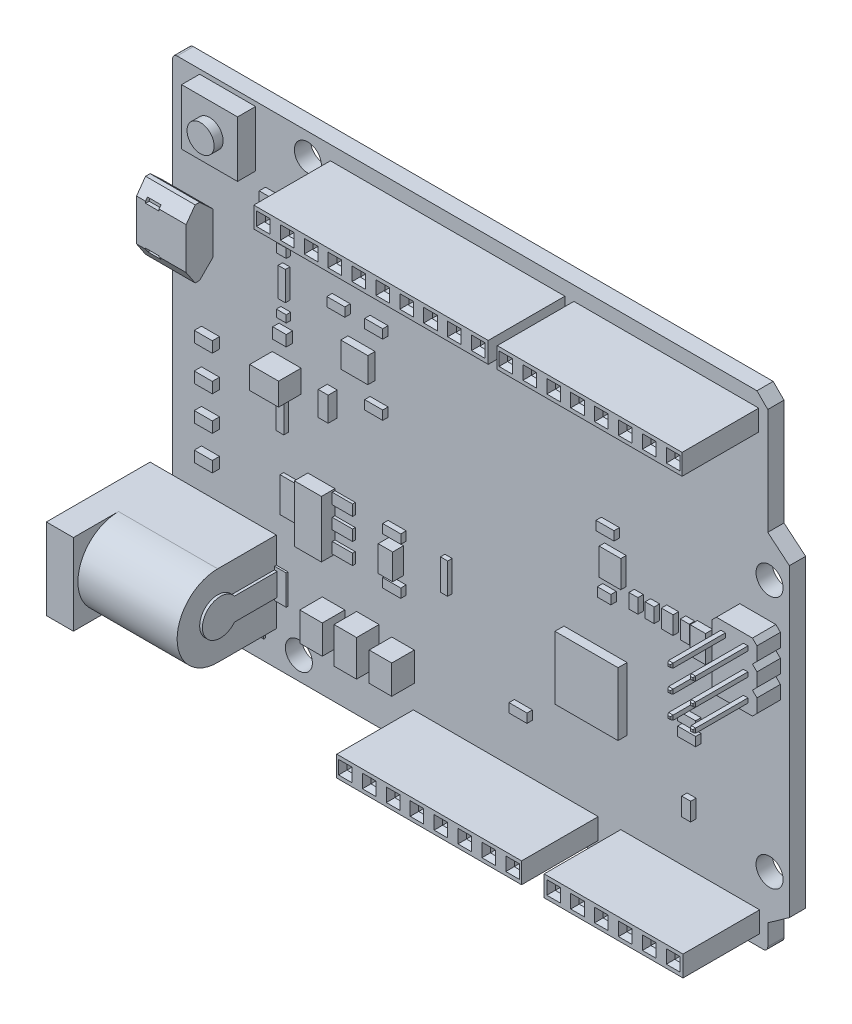
SolidWorks part; units mm, degrees
ref_plane "Front Plane" through (0, 0, 0) normal (0, 0, 1) x (1, 0, 0)
ref_plane "Top Plane" through (0, 0, 0) normal (0, 1, 0) x (1, 0, 0)
ref_plane "Right Plane" through (0, 0, 0) normal (1, 0, 0) x (0, 0, -1)
sketch "Sketch1" plane through (0, 0, 0) normal (0, 0, 1) x (1, 0, 0)
  line L0 (66, -1.2) -> (66, -13)
  line L1 (0.5, 0) -> (64.8, 0)
  line L2 (0, -0.5) -> (0, -52.8)
  line L3 (0.5, -53.3) -> (65.5, -53.3)
  line L4 (68.4, -15) -> (68.4, -48.8)
  line L5 (66, -13) -> (68.4, -15)
  line L6 (68.4, -48.8) -> (66, -50.5)
  line L7 (66, -50.5) -> (66, -52.8)
  line L8 (64.8, 0) -> (66, -1.2)
  arc A0 (65.5, -53.3) -> (66, -52.8) centre (65.5, -52.8) ccw
  arc A1 (0, -52.8) -> (0.5, -53.3) centre (0.5, -52.8) ccw
  arc A2 (0.5, 0) -> (0, -0.5) centre (0.5, -0.5) ccw
  point P12 (66, -53.3)
  point P15 (0, -53.3)
  point P18 (0, 0)
  dimension "D5" = 0.5
  dimension "D1" = 68.4
  dimension "D2" = 53.3
  dimension "D3" = 66
  dimension "D4" = 66
  dimension "D6" = 15
  dimension "D7" = 48.8
  dimension "D8" = 50.5
  dimension "D9" = 45
  dimension "D10" = 1.2
extrude "Boss-Extrude1" add sketch "Sketch1" along normal blind 1.8
sketch "Sketch2" plane through (0, 0, 1.8) normal (0, 0, 1) x (1, 0, 0)
  line L0 (0, -0.5) -> (0, -52.8) construction
  line L1 (64.8, 0) -> (0.5, 0) construction
  line L2 (68.4, -48.8) -> (68.4, -15) construction
  line L3 (0.5, -53.3) -> (65.5, -53.3) construction
  point P0 (15, -2.5)
  point P1 (66.2, -17.5)
  point P2 (66.2, -45.5)
  point P3 (14, -50.8)
  dimension "D1" = 15
  dimension "D2" = 2.5
  dimension "D3" = 2.2
  dimension "D4" = 2.2
  dimension "D5" = 2.5
  dimension "D6" = 14
  dimension "D7" = 17.5
  dimension "D8" = 45.5
hole_wizard "Ø3.0 (3) Diameter Hole2" positions "Sketch6" profile "Sketch7" hole size "Ø3.0" standard "ISO" end condition through all
sketch "Sketch6" plane through (0, 0, 1.8) normal (0, 0, 1) x (1, 0, 0)
  point P0 (15, -2.5)
  point P3 (66.2, -17.5)
  point P6 (66.2, -45.5)
  point P9 (14, -50.8)
sketch "Sketch7" plane through (15, -2.5, 1.8) normal (1, 0, 0) x (0, -1, 0)
  line L0 (0, 0) -> (0, 1.8)
  line L1 (0, 1.8) -> (1.5, 1.8)
  line L2 (1.5, 1.8) -> (1.5, 0)
  line L5 (1.5, 0) -> (0, 0)
  line L11 (0, -6.35) -> (0, 107.95) construction
  dimension "Thru Hole Dia." = 3
  dimension "Thru Hole Depth" = 1.8
sketch "Sketch8" plane through (0, 0, 1.8) normal (0, 0, 1) x (1, 0, 0)
  line L0 (0.5, -53.3) -> (65.5, -53.3) construction
  line L1 (44.5, -1.5683) -> (65, -1.5683)
  line L2 (44.5, -1.5683) -> (44.5, -3.8683)
  line L3 (44.5, -3.8683) -> (65, -3.8683)
  line L4 (65, -1.5683) -> (65, -3.8683)
  line L5 (17.5, -1.5683) -> (43.5, -1.5683)
  line L6 (17.5, -1.5683) -> (17.5, -3.8683)
  line L7 (17.5, -3.8683) -> (43.5, -3.8683)
  line L8 (43.5, -1.5683) -> (43.5, -3.8683)
  line L9 (65.1, -52) -> (49.7, -52)
  line L10 (65.1, -52) -> (65.1, -49.7)
  line L11 (65.1, -49.7) -> (49.7, -49.7)
  line L12 (49.7, -52) -> (49.7, -49.7)
  line L13 (47.2, -52) -> (26.7, -52)
  line L14 (47.2, -52) -> (47.2, -49.7)
  line L15 (47.2, -49.7) -> (26.7, -49.7)
  line L16 (26.7, -52) -> (26.7, -49.7)
  line L17 (68.4, -48.8) -> (68.4, -15) construction
  line L18 (66, -13) -> (66, -1.2) construction
  dimension "D1" = 2.3
  dimension "D2" = 2.3
  dimension "D3" = 2.3
  dimension "D4" = 2.3
  dimension "D5" = 15.4
  dimension "D6" = 1.3
  dimension "D7" = 1.3
  dimension "D8" = 20.5
  dimension "D9" = 2.5
  dimension "D10" = 3.3
  dimension "D11" = 1
  dimension "D12" = 1
  dimension "D13" = 20.5
  dimension "D14" = 26
extrude "Boss-Extrude2" add sketch "Sketch8" along normal blind 8.5
sketch "Sketch10" plane through (0, 0, 10.3) normal (0, 0, 1) x (1, 0, 0)
  line L0 (26.7, -49.7) -> (26.7, -52) construction
  line L1 (26.9, -50.1) -> (28.4, -50.1)
  line L2 (26.9, -50.1) -> (26.9, -51.6)
  line L3 (26.9, -51.6) -> (28.4, -51.6)
  line L4 (28.4, -50.1) -> (28.4, -51.6)
  line L5 (26.7, -52) -> (47.2, -52) construction
  dimension "D1" = 1.5
  dimension "D2" = 1.5
  dimension "D3" = 0.2
  dimension "D4" = 0.4
extrude "Cut-Extrude1" cut sketch "Sketch10" against normal blind 8.5 draft 20
sketch "Sketch11" plane through (0, 0, 10.3) normal (0, 0, 1) x (1, 0, 0)
  line L0 (27.65, -50.85) -> (28.4, -51.6) construction
  line L1 (27.15, -50.35) -> (28.15, -50.35)
  line L2 (27.15, -50.35) -> (27.15, -51.35)
  line L3 (27.15, -51.35) -> (28.15, -51.35)
  line L4 (28.15, -50.35) -> (28.15, -51.35)
  line L5 (27.15, -50.35) -> (28.15, -51.35) construction
  line L6 (27.15, -51.35) -> (28.15, -50.35) construction
  point P0 (27.65, -50.85)
  dimension "D1" = 1
  dimension "D2" = 1
extrude "Cut-Extrude2" cut sketch "Sketch11" against normal blind 8.5
pattern_linear "LPattern1" count 8 spacing 2.65 along (1, 0, 0) of "Cut-Extrude2", "Cut-Extrude1"
sketch "Sketch12" plane through (0, 0, 10.3) normal (0, 0, 1) x (1, 0, 0)
  line L0 (65.1, -49.7) -> (49.7, -49.7) construction
  line L1 (50, -50.1) -> (51.5, -50.1)
  line L2 (50, -50.1) -> (50, -51.6)
  line L3 (50, -51.6) -> (51.5, -51.6)
  line L4 (51.5, -50.1) -> (51.5, -51.6)
  line L5 (49.7, -49.7) -> (49.7, -52) construction
  dimension "D1" = 1.5
  dimension "D2" = 1.5
  dimension "D3" = 0.4
  dimension "D4" = 0.3
extrude "Cut-Extrude3" cut sketch "Sketch12" against normal blind 8.5 draft 20
sketch "Sketch14" plane through (0, 0, 10.3) normal (0, 0, 1) x (1, 0, 0)
  line L0 (50.75, -50.85) -> (51.5, -50.1) construction
  line L1 (50.25, -50.35) -> (51.25, -50.35)
  line L2 (50.25, -50.35) -> (50.25, -51.35)
  line L3 (50.25, -51.35) -> (51.25, -51.35)
  line L4 (51.25, -50.35) -> (51.25, -51.35)
  line L5 (50.25, -50.35) -> (51.25, -51.35) construction
  line L6 (50.25, -51.35) -> (51.25, -50.35) construction
  line L7 (50.75, -50.85) -> (50, -51.6) construction
  line L8 (51.5, -50.1) -> (50, -50.1) construction
  line L9 (50, -50.1) -> (50, -51.6) construction
  point P0 (50.75, -50.85)
  dimension "D1" = 1
  dimension "D2" = 1
  dimension "D3" = 0.25
  dimension "D4" = 0.25
extrude "Cut-Extrude4" cut sketch "Sketch14" against normal blind 8.5
pattern_linear "LPattern2" count 6 spacing 2.65 along (1, 0, 0) of "Cut-Extrude4", "Cut-Extrude3"
sketch "Sketch15" plane through (0, 0, 10.3) normal (0, 0, 1) x (1, 0, 0)
  line L0 (17.5, -1.5683) -> (17.5, -3.8683) construction
  line L1 (17.8, -1.9683) -> (19.3, -1.9683)
  line L2 (17.8, -1.9683) -> (17.8, -3.4683)
  line L3 (17.8, -3.4683) -> (19.3, -3.4683)
  line L4 (19.3, -1.9683) -> (19.3, -3.4683)
  line L5 (43.5, -1.5683) -> (17.5, -1.5683) construction
  point P4 (17.5, -2.7183)
  dimension "D1" = 0.3
  dimension "D2" = 1.5
  dimension "D3" = 0.4
  dimension "D4" = 1.5
extrude "Cut-Extrude5" cut sketch "Sketch15" against normal blind 8.5 draft 20
sketch "Sketch16" plane through (0, 0, 10.3) normal (0, 0, 1) x (1, 0, 0)
  line L0 (18.55, -2.7183) -> (19.3, -3.4683) construction
  line L1 (18.0652, -2.2335) -> (19.0652, -2.2335)
  line L2 (18.0652, -2.2335) -> (18.0652, -3.2335)
  line L3 (18.0652, -3.2335) -> (19.0652, -3.2335)
  line L4 (19.0652, -2.2335) -> (19.0652, -3.2335)
  line L5 (18.0652, -2.2335) -> (19.0652, -3.2335) construction
  line L6 (18.0652, -3.2335) -> (19.0652, -2.2335) construction
  point P0 (18.5652, -2.7335)
  dimension "D1" = 1
extrude "Cut-Extrude6" cut sketch "Sketch16" against normal blind 8.5
pattern_linear "LPattern3" count 10 spacing 2.65 along (1, 0, 0) of "Cut-Extrude5", "Cut-Extrude6"
sketch "Sketch17" plane through (0, 0, 10.3) normal (0, 0, 1) x (1, 0, 0)
  line L0 (65, -1.5683) -> (44.5, -1.5683) construction
  line L1 (44.7, -1.9683) -> (46.2, -1.9683)
  line L2 (44.7, -1.9683) -> (44.7, -3.4683)
  line L3 (44.7, -3.4683) -> (46.2, -3.4683)
  line L4 (46.2, -1.9683) -> (46.2, -3.4683)
  line L5 (44.5, -1.5683) -> (44.5, -3.8683) construction
  dimension "D1" = 0.4
  dimension "D2" = 1.5
  dimension "D3" = 1.5
  dimension "D4" = 0.2
extrude "Cut-Extrude7" cut sketch "Sketch17" against normal blind 8.5 draft 20
sketch "Sketch18" plane through (0, 0, 10.3) normal (0, 0, 1) x (1, 0, 0)
  line L0 (45.45, -2.7183) -> (46.2, -3.4683) construction
  line L1 (44.95, -2.2183) -> (45.95, -2.2183)
  line L2 (44.95, -2.2183) -> (44.95, -3.2183)
  line L3 (44.95, -3.2183) -> (45.95, -3.2183)
  line L4 (45.95, -2.2183) -> (45.95, -3.2183)
  line L5 (44.95, -2.2183) -> (45.95, -3.2183) construction
  line L6 (44.95, -3.2183) -> (45.95, -2.2183) construction
  point P0 (45.45, -2.7183)
  dimension "D1" = 1
extrude "Cut-Extrude8" cut sketch "Sketch18" against normal blind 8.5
pattern_linear "LPattern4" count 8 spacing 2.65 along (1, 0, 0) of "Cut-Extrude8", "Cut-Extrude7"
sketch "Sketch19" plane through (0, 0, 1.8) normal (0, 0, 1) x (1, 0, 0)
  line L0 (68.4, -48.8) -> (68.4, -15) construction
  line L1 (62.4, -21.4) -> (67.4, -21.4)
  line L2 (62.4, -21.4) -> (62.4, -23.4)
  line L3 (62.4, -28.9) -> (67.4, -28.9)
  line L4 (67.4, -21.4) -> (67.4, -23.4)
  line L5 (64.8, 0) -> (0.5, 0) construction
  line L6 (66.9, -26.4) -> (67.4, -25.9)
  line L7 (66.9, -26.4) -> (67.4, -26.9)
  line L10 (62.9, -26.4) -> (62.4, -26.9)
  line L11 (62.9, -26.4) -> (62.4, -25.9)
  line L12 (66.9, -23.9) -> (67.4, -23.4)
  line L13 (66.9, -23.9) -> (67.4, -24.4)
  line L14 (62.9, -23.9) -> (62.4, -24.4)
  line L15 (62.9, -23.9) -> (62.4, -23.4)
  line L16 (62.4, -24.4) -> (62.4, -25.9)
  line L17 (62.4, -26.9) -> (62.4, -28.9)
  line L18 (67.4, -24.4) -> (67.4, -25.9)
  line L19 (67.4, -26.9) -> (67.4, -28.9)
  dimension "D1" = 5
  dimension "D2" = 7.5
  dimension "D3" = 5
  dimension "D4" = 1
  dimension "D5" = 21.4
  dimension "D6" = 2.5
  dimension "D7" = 5
  dimension "D8" = 90
  dimension "D9" = 135
  dimension "D10" = 135
  dimension "D11" = 90
  dimension "D12" = 90
  dimension "D13" = 90
  dimension "D14" = 135
  dimension "D15" = 135
  dimension "D16" = 0.5
  dimension "D17" = 0.5
  dimension "D18" = 0.5
  dimension "D19" = 0.5
extrude "Boss-Extrude3" add sketch "Sketch19" along normal blind 2.6
chamfer "Chamfer1" distance 0.5 angle 45 4 edges at (62.4, -21.4, 3.1) (62.4, -28.9, 3.1) (67.4, -28.9, 3.1) (67.4, -21.4, 3.1)
sketch "Sketch20" plane through (0, 0, 4.4) normal (0, 0, 1) x (1, 0, 0)
  line L0 (66.9, -21.4) -> (62.9, -21.4) construction
  line L1 (63.4, -22.4) -> (63.9, -22.4)
  line L2 (63.4, -22.4) -> (63.4, -22.9)
  line L3 (63.4, -22.9) -> (63.9, -22.9)
  line L4 (63.9, -22.4) -> (63.9, -22.9)
  line L5 (65.9, -22.4) -> (66.4, -22.4)
  line L6 (65.9, -22.4) -> (65.9, -22.9)
  line L7 (65.9, -22.9) -> (66.4, -22.9)
  line L8 (66.4, -22.4) -> (66.4, -22.9)
  line L9 (62.4, -21.9) -> (62.4, -23.4) construction
  line L10 (67.4, -23.4) -> (67.4, -21.9) construction
  point P11 (62.4, -22.65)
  dimension "D1" = 0.5
  dimension "D2" = 0.5
  dimension "D3" = 0.5
  dimension "D4" = 0.5
  dimension "D5" = 2
  dimension "D6" = 1
  dimension "D7" = 1
  dimension "D8" = 1
  dimension "D9" = 1
  dimension "D10" = 1
extrude "Boss-Extrude4" add sketch "Sketch20" along normal blind 6
chamfer "Chamfer2" distance 0.2 angle 30 8 edges at (66.4, -22.65, 10.4) (66.15, -22.9, 10.4) (65.9, -22.65, 10.4) (66.15, -22.4, 10.4) (63.9, -22.65, 10.4) (63.65, -22.4, 10.4) (63.4, -22.65, 10.4) (63.65, -22.9, 10.4) first distance on face at (66.4, -22.65, 7.4) first distance on face at (66.15, -22.9, 7.4) first distance on face at (65.9, -22.65, 7.4) first distance on face at (66.15, -22.4, 7.4) first distance on face at (63.9, -22.65, 7.4) first distance on face at (63.65, -22.4, 7.4) first distance on face at (63.4, -22.65, 7.4) first distance on face at (63.65, -22.9, 7.4)
pattern_linear "LPattern6" count 3 spacing 2.5 along (0, -1, 0) of "Chamfer2", "Boss-Extrude4"
sketch "Sketch21" plane through (0, 0, 1.8) normal (0, 0, 1) x (1, 0, 0)
  line L0 (68.4, -48.8) -> (68.4, -15) construction
  line L1 (43.4, -33.3) -> (50.4, -33.3)
  line L2 (43.4, -33.3) -> (43.4, -40.3)
  line L3 (43.4, -40.3) -> (50.4, -40.3)
  line L4 (50.4, -33.3) -> (50.4, -40.3)
  line L5 (0.5, -53.3) -> (65.5, -53.3) construction
  dimension "D1" = 7
  dimension "D2" = 7
  dimension "D3" = 18
  dimension "D4" = 20
extrude "Boss-Extrude5" add sketch "Sketch21" along normal blind 1
sketch "Sketch22" plane through (0, 0, 1.8) normal (0, 0, 1) x (1, 0, 0)
  line L0 (62.4, -26.9) -> (62.4, -28.4) construction
  line L1 (58.2, -25.3683) -> (59.9, -25.3683)
  line L2 (58.2, -25.3683) -> (58.2, -28.3683)
  line L3 (58.2, -28.3683) -> (59.9, -28.3683)
  line L4 (59.9, -25.3683) -> (59.9, -28.3683)
  line L5 (44.5, -3.8683) -> (65, -3.8683) construction
  point P4 (62.4, -27.65)
  dimension "D1" = 3
  dimension "D2" = 1.7
  dimension "D3" = 2.5
  dimension "D4" = 21.5
extrude "Boss-Extrude6" add sketch "Sketch22" along normal blind 0.8
sketch "Sketch23" plane through (0, 0, 1.8) normal (0, 0, 1) x (1, 0, 0)
  line L0 (58.2, -25.3683) -> (58.2, -28.3683) construction
  line L1 (56.9, -25.5683) -> (57.9, -25.5683)
  line L2 (56.9, -25.5683) -> (56.9, -27.5683)
  line L3 (56.9, -27.5683) -> (57.9, -27.5683)
  line L4 (57.9, -25.5683) -> (57.9, -27.5683)
  line L5 (54.8, -25.5683) -> (56.1, -25.5683)
  line L6 (54.8, -25.5683) -> (54.8, -27.5683)
  line L7 (54.8, -27.5683) -> (56.1, -27.5683)
  line L8 (56.1, -25.5683) -> (56.1, -27.5683)
  line L10 (53, -25.8683) -> (54, -25.8683)
  line L11 (53, -25.8683) -> (53, -27.4683)
  line L12 (53, -27.4683) -> (54, -27.4683)
  line L13 (51.2, -25.8683) -> (52.2, -25.8683)
  line L14 (51.2, -25.8683) -> (51.2, -27.4683)
  line L15 (51.2, -27.4683) -> (52.2, -27.4683)
  line L16 (52.2, -25.8683) -> (52.2, -27.4683)
  line L17 (47.9, -23.0683) -> (50.3, -23.0683)
  line L18 (47.9, -23.0683) -> (47.9, -26.0683)
  line L19 (47.9, -26.0683) -> (50.3, -26.0683)
  line L20 (50.3, -23.0683) -> (50.3, -26.0683)
  line L21 (47.5517, -20.7683) -> (49.5517, -20.7683)
  line L22 (47.5517, -20.7683) -> (47.5517, -21.7683)
  line L23 (47.5517, -21.7683) -> (49.5517, -21.7683)
  line L24 (49.5517, -20.7683) -> (49.5517, -21.7683)
  line L25 (47.7, -27.0683) -> (49.2, -27.0683)
  line L26 (47.7, -27.0683) -> (47.7, -28.0683)
  line L27 (47.7, -28.0683) -> (49.2, -28.0683)
  line L28 (49.2, -27.0683) -> (49.2, -28.0683)
  line L29 (59.9, -25.3683) -> (58.2, -25.3683) construction
  line L30 (54, -25.8683) -> (54, -27.4683)
  dimension "D1" = 0.3
  dimension "D2" = 1
  dimension "D3" = 1.3
  dimension "D4" = 1
  dimension "D5" = 1
  dimension "D6" = 0.2
  dimension "D7" = 0.8
  dimension "D8" = 0.8
  dimension "D9" = 0.8
  dimension "D10" = 0.3
  dimension "D11" = 1.6
  dimension "D12" = 1.6
  dimension "D13" = 0.3
  dimension "D14" = 2
  dimension "D15" = 2
  dimension "D16" = 2.4
  dimension "D17" = 0.9
  dimension "D18" = 3
  dimension "D19" = 0.2
  dimension "D20" = 1
  dimension "D21" = 1.5
  dimension "D22" = 2
  dimension "D23" = 1
  dimension "D24" = 2
  dimension "D25" = 1.3
  dimension "D26" = 1
extrude "Boss-Extrude7" add sketch "Sketch23" along normal blind 0.6
sketch "Sketch24" plane through (0, 0, 1.8) normal (0, 0, 1) x (1, 0, 0)
  line L0 (65.1, -49.7) -> (49.7, -49.7) construction
  line L1 (56.6, -34.5) -> (58.6, -34.5)
  line L2 (56.6, -34.5) -> (56.6, -35.5)
  line L3 (56.6, -35.5) -> (58.6, -35.5)
  line L4 (58.6, -34.5) -> (58.6, -35.5)
  line L5 (56.6, -36) -> (58.6, -36)
  line L6 (56.6, -36) -> (56.6, -37)
  line L7 (56.6, -37) -> (58.6, -37)
  line L8 (58.6, -36) -> (58.6, -37)
  line L9 (57.0515, -42.5) -> (58.0515, -42.5)
  line L10 (57.0515, -42.5) -> (57.0515, -44.5)
  line L11 (57.0515, -44.5) -> (58.0515, -44.5)
  line L12 (58.0515, -42.5) -> (58.0515, -44.5)
  line L13 (37.9, -43.1) -> (39.9, -43.1)
  line L14 (37.9, -43.1) -> (37.9, -44.1)
  line L15 (37.9, -44.1) -> (39.9, -44.1)
  line L16 (39.9, -43.1) -> (39.9, -44.1)
  line L17 (21.9, -22) -> (23.9, -22)
  line L18 (21.9, -22) -> (21.9, -23)
  line L19 (21.9, -23) -> (23.9, -23)
  line L20 (23.9, -22) -> (23.9, -23)
  line L21 (23.9, -32.9) -> (25.9, -32.9)
  line L22 (23.9, -32.9) -> (23.9, -33.9)
  line L23 (23.9, -33.9) -> (25.9, -33.9)
  line L24 (25.9, -32.9) -> (25.9, -33.9)
  line L25 (23.9, -38.1) -> (25.9, -38.1)
  line L26 (23.9, -38.1) -> (23.9, -39.1)
  line L27 (23.9, -39.1) -> (25.9, -39.1)
  line L28 (25.9, -38.1) -> (25.9, -39.1)
  line L29 (50.4, -40.3) -> (50.4, -33.3) construction
  line L30 (43.4, -33.3) -> (43.4, -40.3) construction
  line L31 (47.2, -49.7) -> (26.7, -49.7) construction
  line L33 (43.4, -33.3) -> (43.4, -40.3) construction
  line L34 (17.7, -14.2) -> (19.7, -14.2)
  line L35 (17.7, -14.2) -> (17.7, -15.2)
  line L36 (17.7, -15.2) -> (19.7, -15.2)
  line L37 (19.7, -14.2) -> (19.7, -15.2)
  line L38 (21.9, -14.2) -> (23.9, -14.2)
  line L39 (21.9, -14.2) -> (21.9, -15.2)
  line L40 (21.9, -15.2) -> (23.9, -15.2)
  line L41 (23.9, -14.2) -> (23.9, -15.2)
  dimension "D1" = 1
  dimension "D2" = 1
  dimension "D3" = 2
  dimension "D4" = 2
  dimension "D5" = 1
  dimension "D6" = 2
  dimension "D7" = 1
  dimension "D8" = 1
  dimension "D9" = 2
  dimension "D10" = 2
  dimension "D11" = 2
  dimension "D12" = 1
  dimension "D13" = 2
  dimension "D14" = 1
  dimension "D15" = 5.2
  dimension "D16" = 5.5
  dimension "D17" = 0.5
  dimension "D18" = 6.2
  dimension "D19" = 3.5
  dimension "D20" = 5.6
  dimension "D21" = 10.6
  dimension "D22" = 4.2
  dimension "D23" = 17.5
  dimension "D24" = 19.5
  dimension "D25" = 9.9
  dimension "D26" = 2
  dimension "D27" = 2
  dimension "D28" = 2.2
  dimension "D29" = 19.5
  dimension "D30" = 6.8
  dimension "D31" = 6.8
  dimension "D32" = 1
  dimension "D33" = 1
  dimension "D34" = 17.5
extrude "Boss-Extrude8" add sketch "Sketch24" along normal blind 0.6
sketch "Sketch25" plane through (0, 0, 1.8) normal (0, 0, 1) x (1, 0, 0)
  line L0 (17.7, -15.2) -> (19.7, -15.2) construction
  line L1 (19.45, -17.4) -> (22.45, -17.4)
  line L2 (19.45, -17.4) -> (19.45, -20.2)
  line L3 (19.45, -20.2) -> (22.45, -20.2)
  line L4 (22.45, -17.4) -> (22.45, -20.2)
  line L5 (23.9, -23) -> (23.9, -22) construction
  dimension "D1" = 2.2
  dimension "D2" = 2.8
  dimension "D3" = 3
  dimension "D4" = 1.45
extrude "Boss-Extrude9" add sketch "Sketch25" along normal blind 0.8
sketch "Sketch26" plane through (0, 0, 1.8) normal (0, 0, 1) x (1, 0, 0)
  line L0 (25.9, -38.1) -> (23.9, -38.1) construction
  line L1 (24, -34.4854) -> (25.6, -34.4854)
  line L2 (24, -34.4854) -> (24, -37.35)
  line L3 (24, -37.35) -> (25.6, -37.35)
  line L4 (25.6, -34.4854) -> (25.6, -37.35)
  line L5 (43.4, -33.3) -> (43.4, -40.3) construction
  dimension "D1" = 1.6
  dimension "D2" = 2.8646
  dimension "D3" = 0.75
  dimension "D4" = 17.8
extrude "Boss-Extrude10" add sketch "Sketch26" along normal blind 1.2
sketch "Sketch27" plane through (0, 0, 1.8) normal (0, 0, 1) x (1, 0, 0)
  line L0 (43.4, -33.3) -> (43.4, -40.3) construction
  line L1 (24.3, -44.5) -> (26.8, -44.5)
  line L2 (24.3, -44.5) -> (24.3, -46.5)
  line L3 (24.3, -46.5) -> (26.8, -46.5)
  line L4 (26.8, -44.5) -> (26.8, -46.5)
  line L5 (16.6, -44.5) -> (19.1, -44.5)
  line L6 (16.6, -44.5) -> (16.6, -46.5)
  line L7 (16.6, -46.5) -> (19.1, -46.5)
  line L8 (19.1, -44.5) -> (19.1, -46.5)
  line L9 (20.4, -43.4) -> (22.9, -43.4)
  line L10 (20.4, -43.4) -> (20.4, -47.4)
  line L11 (20.4, -47.4) -> (22.9, -47.4)
  line L12 (22.9, -43.4) -> (22.9, -47.4)
  line L13 (47.2, -49.7) -> (26.7, -49.7) construction
  line L14 (47.2, -49.7) -> (26.7, -49.7) construction
  dimension "D1" = 2.5
  dimension "D2" = 2.5
  dimension "D3" = 2
  dimension "D4" = 2
  dimension "D5" = 16.6
  dimension "D6" = 5.2
  dimension "D7" = 3.2
  dimension "D8" = 2.3
  dimension "D9" = 2.5
  dimension "D10" = 4
  dimension "D11" = 1.4
extrude "Boss-Extrude11" add sketch "Sketch27" along normal blind 2.5
sketch "Sketch28" plane through (0, 0, 1.8) normal (0, 0, 1) x (1, 0, 0)
  line L1 (24.3, -44.5) -> (26.8, -44.5)
  line L2 (24.3, -44.5) -> (24.3, -43.9)
  line L3 (24.3, -43.9) -> (26.8, -43.9)
  line L4 (26.8, -44.5) -> (26.8, -43.9)
  line L5 (24.3, -46.5) -> (26.8, -46.5)
  line L6 (24.3, -46.5) -> (24.3, -47.1)
  line L7 (24.3, -47.1) -> (26.8, -47.1)
  line L8 (26.8, -46.5) -> (26.8, -47.1)
  line L9 (19.1, -46.5) -> (16.6, -46.5)
  line L10 (19.1, -46.5) -> (19.1, -47.1)
  line L11 (19.1, -47.1) -> (16.6, -47.1)
  line L12 (16.6, -46.5) -> (16.6, -47.1)
  line L13 (16.6, -44.5) -> (19.1, -44.5)
  line L14 (16.6, -44.5) -> (16.6, -43.9)
  line L15 (16.6, -43.9) -> (19.1, -43.9)
  line L16 (19.1, -44.5) -> (19.1, -43.9)
  dimension "D1" = 0.6
  dimension "D2" = 0.6
  dimension "D5" = 0.6
  dimension "D6" = 0.6
extrude "Boss-Extrude12" add sketch "Sketch28" along normal blind 2.5
sketch "Sketch30" plane through (0, 0, 1.8) normal (0, 0, 1) x (1, 0, 0)
  line L0 (0.5, -53.3) -> (65.5, -53.3) construction
  line L1 (11.5, -40.5) -> (-2.5, -40.5)
  line L2 (11.5, -40.5) -> (11.5, -49.5)
  line L3 (11.5, -49.5) -> (-2.5, -49.5)
  line L4 (-2.5, -40.5) -> (-2.5, -49.5)
  line L5 (0, -0.5) -> (0, -52.8) construction
  dimension "D1" = 14
  dimension "D2" = 9
  dimension "D3" = 3.8
  dimension "D4" = 2.5
extrude "Boss-Extrude13" add sketch "Sketch30" along normal blind 6.5
sketch "Sketch31" plane through (-2.5, 0, 0) normal (-1, 0, 0) x (0, 0, 1)
  line L0 (8.3, -40.5) -> (8.3, -49.5) construction
  circle A0 centre (8.3, -45) radius 4.5
  dimension "D1" = 9
extrude "Boss-Extrude14" add sketch "Sketch31" against normal blind 14
sketch "Sketch32" plane through (-2.5, 0, 0) normal (-1, 0, 0) x (0, 0, 1)
  line L1 (8.3, -40.5) -> (13.3, -40.5)
  line L2 (8.3, -40.5) -> (8.3, -49.5)
  line L3 (8.3, -49.5) -> (13.3, -49.5)
  line L4 (13.3, -40.5) -> (13.3, -49.5)
  dimension "D1" = 5
extrude "Boss-Extrude15" add sketch "Sketch32" against normal blind 3
sketch "Sketch33" plane through (-2.5, 0, 0) normal (-1, 0, 0) x (0, 0, 1)
  line L0 (13.3, -49.5) -> (1.8, -49.5) construction
  line L1 (13.3, -49.5) -> (13.3, -40.5) construction
  circle A0 centre (8.3, -45) radius 2.8159
  dimension "D1" = 4.5
  dimension "D2" = 5
extrude "Cut-Extrude9" cut sketch "Sketch33" against normal blind 10
sketch "Sketch34" plane through (7.5, 0, 0) normal (-1, 0, 0) x (0, 0, 1)
  circle A0 centre (8.3, -45) radius 1.25
  dimension "D1" = 2.5
extrude "Boss-Extrude16" add sketch "Sketch34" along normal blind 9
fillet "Fillet1" radius 1.25 1 edges at (-1.5, -46.25, 8.3)
sketch "Sketch35" plane through (0, -49.5, 0) normal (0, -1, 0) x (1, 0, 0)
  line L0 (0, 1.8) -> (11.5, 1.8) construction
  line L1 (7.5, 1.8) -> (10, 1.8)
  line L2 (7.5, 1.8) -> (7.5, 6.3)
  line L3 (7.5, 6.3) -> (10, 6.3)
  line L4 (10, 1.8) -> (10, 6.3)
  line L5 (11.5, 8.3) -> (11.5, 1.8) construction
  dimension "D1" = 2.5
  dimension "D2" = 4.5
  dimension "D3" = 1.5
extrude "Boss-Extrude17" add sketch "Sketch35" along normal blind 0.2
sketch "Sketch36" plane through (11.5, 0, 0) normal (1, 0, 0) x (0, 0, -1)
  line L0 (-1.8, -49.5) -> (-1.8, -40.5) construction
  line L1 (-6.7388, -46.25) -> (-1.8, -46.25)
  line L3 (-6.7388, -43.75) -> (-1.8, -43.75)
  line L4 (-1.8, -46.25) -> (-1.8, -43.75)
  line L5 (-8.3, -40.5) -> (-1.8, -40.5) construction
  line L6 (-1.8, -49.5) -> (-6.3, -49.5) construction
  arc A0 (-6.7388, -43.75) -> (-6.7388, -46.25) centre (-8.3, -45) ccw
  dimension "D2" = 4
  dimension "D1" = 2.5
  dimension "D3" = 3.25
  dimension "D4" = 3.25
extrude "Boss-Extrude18" add sketch "Sketch36" along normal blind 0.3
sketch "Sketch37" plane through (0, 0, 0) normal (-1, 0, 0) x (0, 0, 1)
  line L0 (1.8, -12.7) -> (3.3, -11.3)
  line L2 (1.8, -0.5) -> (1.8, -40.5) construction
  line L3 (3.3, -11.3) -> (3.8, -11.3)
  line L4 (3.8, -11.3) -> (4.8, -12.7)
  line L5 (4.8, -12.7) -> (4.8, -17.3)
  line L6 (3.3, -11.3) -> (3.3, -18.8)
  line L7 (3.3, -18.8) -> (1.8, -17.3)
  line L8 (3.3, -18.8) -> (3.8, -18.8)
  line L9 (3.8, -18.8) -> (4.8, -17.3)
  line L10 (1.8, -12.7) -> (1.8, -17.3)
  line L11 (3.4577, -11.7) -> (3.5942, -11.7)
  line L12 (3.5942, -11.7) -> (4.4, -12.8282)
  line L13 (4.4, -12.8282) -> (4.4, -17.1789)
  line L14 (3.5859, -18.4) -> (4.4, -17.1789)
  line L15 (3.4657, -18.4) -> (3.5859, -18.4)
  line L16 (3.4657, -18.4) -> (2.2, -17.1343)
  line L17 (2.2, -12.8738) -> (2.2, -17.1343)
  line L18 (2.2, -12.8738) -> (3.4577, -11.7)
  line L19 (1.8, 0) -> (0, 0) construction
  line L20 (2.2, -12.8738) -> (3.5729, -11.5924) construction
  line L21 (3.3, -11.7) -> (3.5942, -11.7) construction
  line L22 (3.3, -18.4) -> (3.5859, -18.4) construction
  line L23 (3.5828, -18.5172) -> (2.2, -17.1343) construction
  line M5 (1.8, -40.5) -> (1.8, -0.5)
  dimension "D1" = 3
  dimension "D2" = 1.5
  dimension "D3" = 0.5
  dimension "D4" = 7.5
  dimension "D5" = 1.4
  dimension "D6" = 0.4
  dimension "D7" = 11.3
extrude "Boss-Extrude19" add sketch "Sketch37" against normal blind 4.5 and the other way blind 1 contours L6 L18 L11 L12 L13 L14 L15 L16 L8 L9 L5 L4 L3 | L17 L18 L6 L0 L7 L16 M5
sketch "Sketch38" plane through (4.5, 0, 0) normal (1, 0, 0) x (0, 0, -1)
  line L0 (-4.4, -12.8282) -> (-4.4, -17.1789)
  line L1 (-4.4, -17.1789) -> (-3.5921, -18.5321)
  line L2 (-3.5921, -18.5321) -> (-3.2472, -18.5321)
  line L3 (-3.2472, -18.5321) -> (-1.9826, -17.1789)
  line L4 (-1.9826, -17.1789) -> (-1.9826, -12.8282)
  line L5 (-1.9826, -12.8282) -> (-3.4766, -11.5142)
  line L6 (-3.4766, -11.5142) -> (-3.7841, -11.5339)
  line L7 (-3.7841, -11.5339) -> (-4.5864, -12.9086)
  line L8 (-4.5864, -12.9086) -> (-4.4, -17.1789)
  line M1 (-2.2, -12.8738) -> (-2.2, -17.1343)
  line M2 (-2.2, -17.1343) -> (-3.4657, -18.4)
  line M3 (-3.4657, -18.4) -> (-3.5859, -18.4)
  line M4 (-3.5859, -18.4) -> (-4.4, -17.1789)
  line M5 (-4.4, -17.1789) -> (-4.4, -12.8282)
  line M6 (-4.4, -12.8282) -> (-3.5942, -11.7)
  line M7 (-3.5942, -11.7) -> (-3.4577, -11.7)
  line M8 (-3.4577, -11.7) -> (-2.2, -12.8738)
extrude "Boss-Extrude20" add sketch "Sketch38" against normal blind 1 contours M1 M8 M7 M6 M5 M4 M3 M2
sketch "Sketch39" plane through (3.5, 0, 0) normal (-1, 0, 0) x (0, 0, 1)
  line L0 (4.4, -12.8282) -> (4.4, -17.1789) construction
  line L1 (3.9, -13.0032) -> (3.4, -13.0032)
  line L2 (3.9, -13.0032) -> (3.9, -17.0032)
  line L3 (3.9, -17.0032) -> (3.4, -17.0032)
  line L4 (3.4, -13.0032) -> (3.4, -17.0032)
  dimension "D1" = 0.5
  dimension "D2" = 0.5
  dimension "D3" = 4
  dimension "D4" = 0.175
  dimension "D5" = 0.1757
extrude "Boss-Extrude21" add sketch "Sketch39" along normal blind 4
sketch "Sketch41" plane through (0, 0, 4.8) normal (0, 0, 1) x (1, 0, 0)
  line L0 (-1, -11.3) -> (4.5, -11.3) construction
  line L1 (0, -12.4) -> (1.5, -12.4)
  line L2 (0, -12.4) -> (0, -12.9)
  line L3 (0, -12.9) -> (1.5, -12.9)
  line L4 (1.5, -12.4) -> (1.5, -12.9)
  line L5 (0, -17.2) -> (1.5, -17.2)
  line L6 (0, -17.2) -> (0, -17.7)
  line L7 (0, -17.7) -> (1.5, -17.7)
  line L8 (1.5, -17.2) -> (1.5, -17.7)
  line L9 (-1, -18.8) -> (4.5, -18.8) construction
  line L10 (-1, -11.3) -> (-1, -12.7) construction
  line L11 (-1, -12.7) -> (-1, -17.3) construction
  dimension "D1" = 1.1
  dimension "D2" = 0.5
  dimension "D3" = 0.5
  dimension "D4" = 1.1
  dimension "D5" = 1.5
  dimension "D6" = 1.5
  dimension "D7" = 1
  dimension "D8" = 1
extrude "Cut-Extrude10" cut sketch "Sketch41" against normal blind 1
sketch "Sketch43" plane through (0, 0, 1.8) normal (0, 0, 1) x (1, 0, 0)
  line L0 (64.8, 0) -> (0.5, 0) construction
  line L1 (3, -0.5) -> (9.2, -0.5)
  line L2 (3, -0.5) -> (3, -6.7)
  line L3 (3, -6.7) -> (9.2, -6.7)
  line L4 (9.2, -0.5) -> (9.2, -6.7)
  line L5 (0, -0.5) -> (0, -12.7) construction
  dimension "D1" = 6.2
  dimension "D2" = 6.2
  dimension "D3" = 0.5
  dimension "D4" = 3
extrude "Boss-Extrude22" add sketch "Sketch43" along normal blind 2
sketch "Sketch44" plane through (0, 0, 3.8) normal (0, 0, 1) x (1, 0, 0)
  line L0 (3, -0.5) -> (3, -6.7) construction
  line L1 (9.2, -0.5) -> (3, -0.5) construction
  circle A0 centre (6.1, -3.6) radius 1.5
  dimension "D3" = 3
  dimension "D1" = 3.1
  dimension "D2" = 3.1
extrude "Boss-Extrude23" add sketch "Sketch44" along normal blind 1
sketch "Sketch45" plane through (0, 0, 1.8) normal (0, 0, 1) x (1, 0, 0)
  line L0 (9.2, -6.7) -> (9.2, -0.5) construction
  line L1 (10.3, -7.7) -> (14.8, -7.7)
  line L2 (10.3, -7.7) -> (10.3, -10.7)
  line L3 (10.3, -10.7) -> (14.8, -10.7)
  line L4 (14.8, -7.7) -> (14.8, -10.7)
  line L5 (3, -6.7) -> (9.2, -6.7) construction
  dimension "D1" = 4.5
  dimension "D2" = 3
  dimension "D3" = 1.1
  dimension "D4" = 1
extrude "Boss-Extrude24" add sketch "Sketch45" along normal blind 0.7
sketch "Sketch46" plane through (0, 0, 1.8) normal (0, 0, 1) x (1, 0, 0)
  line L0 (10.3, -10.7) -> (14.8, -10.7) construction
  line L1 (13.1, -12.9) -> (12, -12.9)
  line L2 (13.1, -12.9) -> (13.1, -11.9)
  line L3 (13.1, -11.9) -> (12, -11.9)
  line L4 (12, -12.9) -> (12, -11.9)
  line L5 (12.2, -14.0036) -> (13, -14.0036)
  line L6 (12.2, -14.0036) -> (12.2, -17.2036)
  line L7 (12.2, -17.2036) -> (13, -17.2036)
  line L8 (13, -14.0036) -> (13, -17.2036)
  line L9 (12, -18.3036) -> (13.1, -18.3036)
  line L10 (12, -18.3036) -> (12, -19.1036)
  line L11 (12, -19.1036) -> (13.1, -19.1036)
  line L12 (13.1, -18.3036) -> (13.1, -19.1036)
  line L13 (14.8, -10.7) -> (14.8, -7.7) construction
  line L17 (11.9692, -26.7892) -> (12.8299, -26.7892)
  line L18 (11.9692, -26.7892) -> (11.9692, -29.9799)
  line L19 (11.9692, -29.9799) -> (12.8299, -29.9799)
  line L20 (12.8299, -26.7892) -> (12.8299, -29.9799)
  dimension "D1" = 1
  dimension "D2" = 1.1
  dimension "D3" = 1.2
  dimension "D4" = 0.8
  dimension "D5" = 3.2
  dimension "D6" = 1.8
  dimension "D7" = 1.7
  dimension "D8" = 1.1
  dimension "D9" = 0.8
  dimension "D10" = 1.1
  dimension "D11" = 0
extrude "Boss-Extrude25" add sketch "Sketch46" along normal blind 0.5
sketch "Sketch47" plane through (0, 0, 1.8) normal (0, 0, 1) x (1, 0, 0)
  line L0 (12, -19.1036) -> (13.1, -19.1036) construction
  line L1 (11.8, -20.0036) -> (13.3, -20.0036)
  line L2 (11.8, -20.0036) -> (11.8, -21.2036)
  line L3 (11.8, -21.2036) -> (13.3, -21.2036)
  line L4 (13.3, -20.0036) -> (13.3, -21.2036)
  line L5 (14.8, -10.7) -> (14.8, -7.7) construction
  dimension "D1" = 1.5
  dimension "D2" = 1.2
  dimension "D3" = 0.9
  dimension "D4" = 1.5
extrude "Boss-Extrude26" add sketch "Sketch47" along normal blind 0.7
sketch "Sketch48" plane through (0, 0, 1.8) normal (0, 0, 1) x (1, 0, 0)
  line L0 (19.45, -17.4) -> (19.45, -20.2) construction
  line L1 (11.05, -23.1036) -> (14.25, -23.1036)
  line L2 (11.05, -23.1036) -> (11.05, -25.6036)
  line L3 (11.05, -25.6036) -> (14.25, -25.6036)
  line L4 (14.25, -23.1036) -> (14.25, -25.6036)
  line L5 (11.8, -21.2036) -> (13.3, -21.2036) construction
  dimension "D1" = 3.2
  dimension "D2" = 2.5
  dimension "D3" = 5.2
  dimension "D4" = 1.9
extrude "Boss-Extrude27" add sketch "Sketch48" along normal blind 2.5
sketch "Sketch49" plane through (0, 0, 1.8) normal (0, 0, 1) x (1, 0, 0)
  line L0 (0, -17.3) -> (0, -40.5) construction
  line L1 (15, -32.8) -> (18, -32.8)
  line L2 (15, -32.8) -> (15, -39.1)
  line L3 (15, -39.1) -> (18, -39.1)
  line L4 (18, -32.8) -> (18, -39.1)
  line L5 (19.1, -43.9) -> (16.6, -43.9) construction
  point P6 (17.85, -43.9)
  dimension "D1" = 3
  dimension "D2" = 6.3
  dimension "D3" = 15
  dimension "D4" = 4.8
extrude "Boss-Extrude28" add sketch "Sketch49" along normal blind 1.5
sketch "Sketch50" plane through (0, 0, 1.8) normal (0, 0, 1) x (1, 0, 0)
  line L0 (14.25, -25.6036) -> (14.25, -23.1036) construction
  line L1 (17.15, -23.2) -> (18.25, -23.2)
  line L2 (17.15, -23.2) -> (17.15, -25.9)
  line L3 (17.15, -25.9) -> (18.25, -25.9)
  line L4 (18.25, -23.2) -> (18.25, -25.9)
  line L5 (19.45, -20.2) -> (22.45, -20.2) construction
  dimension "D1" = 1.1
  dimension "D2" = 2.7
  dimension "D3" = 2.9
  dimension "D4" = 3
extrude "Boss-Extrude29" add sketch "Sketch50" along normal blind 1
sketch "Sketch51" plane through (0, 0, 1.8) normal (0, 0, 1) x (1, 0, 0)
  line L0 (25.9, -33.9) -> (25.9, -32.9) construction
  line L1 (30.2, -33) -> (31, -33)
  line L2 (30.2, -33) -> (30.2, -36.4)
  line L3 (30.2, -36.4) -> (31, -36.4)
  line L4 (31, -33) -> (31, -36.4)
  line L5 (26.8, -43.9) -> (24.3, -43.9) construction
  point P4 (25.9, -33.4)
  dimension "D1" = 0.8
  dimension "D2" = 3.4
  dimension "D3" = 4.3
  dimension "D4" = 7.5
extrude "Boss-Extrude30" add sketch "Sketch51" along normal blind 0.5
sketch "Sketch52" plane through (0, 0, 1.8) normal (0, 0, 1) x (1, 0, 0)
  line L0 (0, -17.3) -> (0, -40.5) construction
  line L1 (3.2, -24.6) -> (5.2, -24.6)
  line L2 (3.2, -24.6) -> (3.2, -25.8)
  line L3 (3.2, -25.8) -> (5.2, -25.8)
  line L4 (5.2, -24.6) -> (5.2, -25.8)
  line L5 (3.2, -28.5) -> (5.2, -28.5)
  line L6 (3.2, -28.5) -> (3.2, -29.7)
  line L7 (3.2, -29.7) -> (5.2, -29.7)
  line L8 (5.2, -28.5) -> (5.2, -29.7)
  line L9 (3.2, -32.3) -> (5.2, -32.3)
  line L10 (3.2, -32.3) -> (3.2, -33.5)
  line L11 (3.2, -33.5) -> (5.2, -33.5)
  line L12 (5.2, -32.3) -> (5.2, -33.5)
  line L13 (3.2, -36.1) -> (5.2, -36.1)
  line L14 (3.2, -36.1) -> (3.2, -37.3)
  line L15 (3.2, -37.3) -> (5.2, -37.3)
  line L16 (5.2, -36.1) -> (5.2, -37.3)
  line L17 (11.5, -40.5) -> (0, -40.5) construction
  dimension "D1" = 2
  dimension "D2" = 2
  dimension "D3" = 2
  dimension "D4" = 2
  dimension "D5" = 1.2
  dimension "D6" = 1.2
  dimension "D7" = 1.2
  dimension "D8" = 1.2
  dimension "D9" = 3.2
  dimension "D10" = 3.2
  dimension "D11" = 3.2
  dimension "D12" = 3.2
  dimension "D13" = 3.2
  dimension "D14" = 2.6
  dimension "D15" = 2.6
  dimension "D16" = 2.7
extrude "Boss-Extrude31" add sketch "Sketch52" along normal blind 0.8
sketch "Sketch53" plane through (0, 0, 1.8) normal (0, 0, 1) x (1, 0, 0)
  line L0 (10, -49.5) -> (11.5, -49.5) construction
  line L1 (6.8, -51) -> (10.3, -51)
  line L2 (6.8, -51) -> (6.8, -49.5)
  line L3 (6.8, -49.5) -> (10.3, -49.5)
  line L4 (10.3, -51) -> (10.3, -49.5)
  line L5 (11.5, -49.5) -> (11.5, -40.5) construction
  line L6 (12.8, -46.7) -> (11.2762, -46.7)
  line L7 (12.8, -46.7) -> (12.8, -43.4)
  line L8 (12.8, -43.4) -> (11.2762, -43.4)
  line L9 (11.2762, -46.7) -> (11.2762, -43.4)
  line L10 (11.8, -47) -> (11.8, -43) construction
  dimension "D1" = 1.5
  dimension "D2" = 3.5
  dimension "D3" = 1.2
  dimension "D4" = 1
  dimension "D5" = 3.3
  dimension "D6" = 2.8
extrude "Boss-Extrude32" add sketch "Sketch53" along normal blind 0.2
sketch "Sketch54" plane through (0, 0, 1.8) normal (0, 0, 1) x (1, 0, 0)
  line L1 (20.2563, -34.1969) -> (17.5639, -34.1969)
  line L2 (20.2563, -34.1969) -> (20.2563, -32.9969)
  line L3 (20.2563, -32.9969) -> (17.5639, -32.9969)
  line L4 (17.5639, -34.1969) -> (17.5639, -32.9969)
  line L5 (20.2563, -36.6062) -> (17.2579, -36.6062)
  line L6 (20.2563, -36.6062) -> (20.2563, -35.4062)
  line L7 (20.2563, -35.4062) -> (17.2579, -35.4062)
  line L8 (17.2579, -36.6062) -> (17.2579, -35.4062)
  line L9 (20.2563, -38.9253) -> (17.2579, -38.9253)
  line L10 (20.2563, -38.9253) -> (20.2563, -37.7253)
  line L11 (20.2563, -37.7253) -> (17.2579, -37.7253)
  line L12 (17.2579, -38.9253) -> (17.2579, -37.7253)
  dimension "D1" = 1.2
  dimension "D2" = 1.2
  dimension "D3" = 1.2
extrude "Boss-Extrude33" add sketch "Sketch54" along normal blind 0.3
sketch "Sketch55" plane through (0, 0, 1.8) normal (0, 0, 1) x (1, 0, 0)
  line L1 (12.3201, -34.1028) -> (15.3565, -34.1028)
  line L2 (12.3201, -34.1028) -> (12.3201, -37.943)
  line L3 (12.3201, -37.943) -> (15.3565, -37.943)
  line L4 (15.3565, -34.1028) -> (15.3565, -37.943)
extrude "Boss-Extrude34" add sketch "Sketch55" along normal blind 0.4
